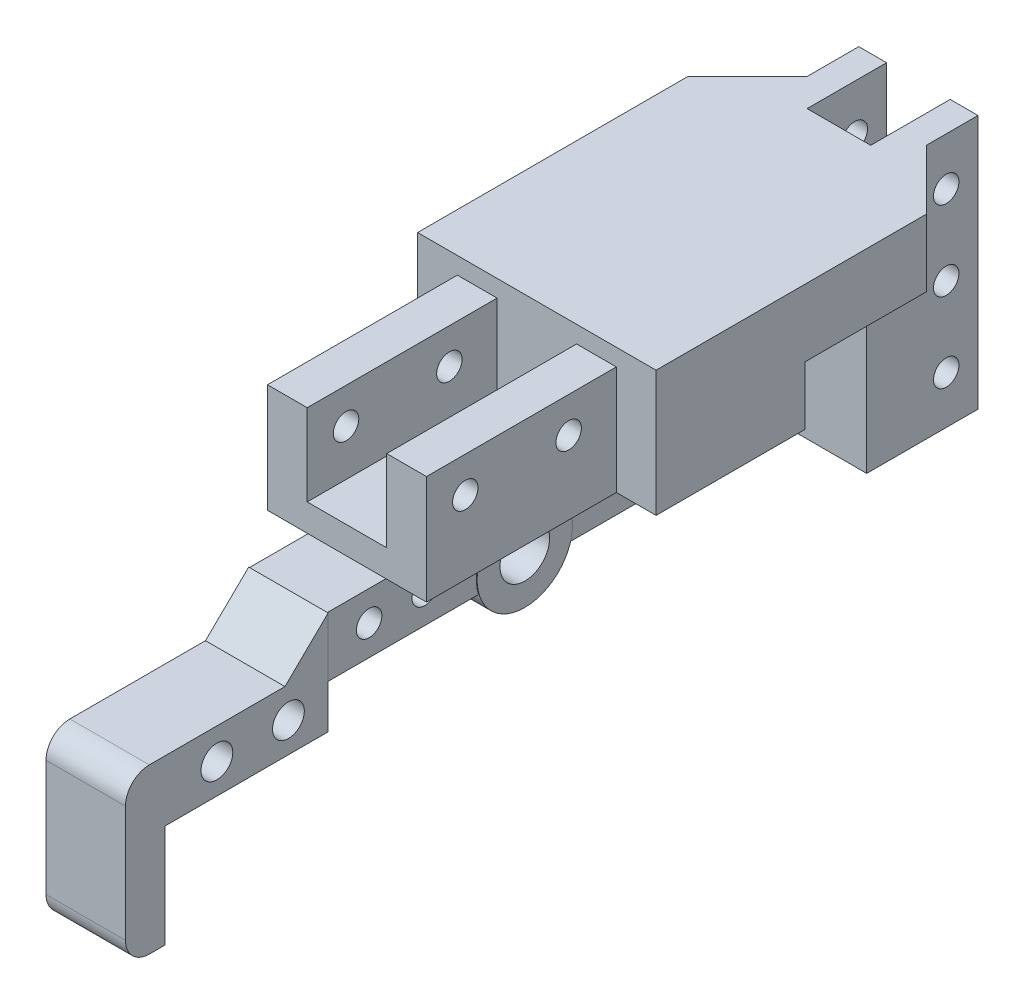
SolidWorks part; units mm, degrees
ref_plane "前视基准面" through (0, 0, 0) normal (0, 0, 1) x (1, 0, 0)
ref_plane "上视基准面" through (0, 0, 0) normal (0, 1, 0) x (1, 0, 0)
ref_plane "右视基准面" through (0, 0, 0) normal (1, 0, 0) x (0, 0, -1)
sketch "草图2" plane through (0, 0, 0) normal (1, 0, 0) x (0, 0, -1)
  line L0 (7, 0) -> (32.5, 0) construction
  line L2 (44.75, 3.775) -> (-5.25, 3.775)
  line L3 (44.75, 3.775) -> (44.75, -3.775)
  line L4 (44.75, -3.775) -> (-5.25, -3.775)
  line L5 (-5.25, 3.775) -> (-5.25, -3.775)
  line L6 (44.75, 3.775) -> (-5.25, -3.775) construction
  line L7 (44.75, -3.775) -> (-5.25, 3.775) construction
  circle A0 centre (0, 0) radius 1.6
  circle A1 centre (7, 0) radius 1.6
  circle A2 centre (32.5, 0) radius 1.6
  circle A3 centre (39.5, 0) radius 1.6
  point P9 (19.75, 0)
  dimension "D1" = 25.5
  dimension "D2" = 7
  dimension "D3" = 3.775
extrude "凸台-拉伸1" add sketch "草图2" along normal mid plane 9.8
sketch "草图3" plane through (0, 0, 0) normal (1, 0, 0) x (0, 0, -1)
  line L0 (7, 13) -> (20, 13) construction
  line L1 (2.1144, 3.775) -> (2.1144, 17.4551)
  line L2 (44.75, 3.775) -> (-5.25, 3.775) construction
  line L3 (2.1144, 17.4551) -> (26, 17.4551)
  line L4 (26, 17.4551) -> (26, 3.775)
  line L5 (26, 3.775) -> (2.1144, 3.775)
  circle A0 centre (7, 13) radius 1.6
  circle A1 centre (20, 13) radius 1.6
  point P0 (7, 0)
  point P6 (13.5, 13)
  dimension "D1" = 13
  dimension "D3" = 3.2
  dimension "D4" = 3.2
  dimension "D2" = 6
extrude "凸台-拉伸2" add sketch "草图3" along normal mid plane 20
sketch "草图4" plane through (0, 0, -2.1144) normal (0, 0, 1) x (1, 0, 0)
  line L0 (10, 17.4551) -> (-10, 17.4551) construction
  line L1 (5, 7.1905) -> (-5, 7.1905)
  line L2 (5, 7.1905) -> (5, 17.4551)
  line L3 (5, 17.4551) -> (-5, 17.4551)
  line L4 (-5, 7.1905) -> (-5, 17.4551)
  line L5 (5, 7.1905) -> (-5, 17.4551) construction
  line L6 (5, 17.4551) -> (-5, 7.1905) construction
  point P0 (0, 12.3228)
extrude "切除-拉伸1" cut sketch "草图4" against normal through all
sketch "草图6" plane through (0, 0, 0) normal (1, 0, 0) x (0, 0, -1)
  line L0 (70, 3.6) -> (70, 13.6) construction
  line L2 (74, -12.4) -> (60, -12.4)
  line L3 (74, -12.4) -> (74, 19.6)
  line L4 (74, 19.6) -> (60, 19.6)
  line L5 (60, -12.4) -> (60, 19.6)
  line L6 (74, -12.4) -> (60, 19.6) construction
  line L7 (74, 19.6) -> (60, -12.4) construction
  circle A0 centre (70, 3.6) radius 1.6
  circle A1 centre (70, 13.6) radius 1.6
  circle A2 centre (70, -6.4) radius 1.6
  point P4 (70, 8.6)
  point P9 (67, 3.6)
  dimension "D1" = 60
  dimension "D6" = 10
  dimension "D2" = 3.6
  dimension "D3" = 10
  dimension "D4" = 4
  dimension "D5" = 14
  dimension "D7" = 6
  dimension "D8" = 6
extrude "凸台-拉伸4" add sketch "草图6" along normal mid plane 15 separate body
sketch "草图7" plane through (0, 0, -74) normal (0, 0, 1) x (1, 0, 0)
  line L0 (7.5, 19.6) -> (-7.5, 19.6) construction
  line L1 (-4, 19.6) -> (4, 19.6)
  line L2 (-4, 19.6) -> (-4, -12.4)
  line L3 (-4, -12.4) -> (4, -12.4)
  line L4 (4, 19.6) -> (4, -12.4)
  line L5 (7.5, -12.4) -> (-7.5, -12.4) construction
extrude "切除-拉伸2" cut sketch "草图7" along normal blind 10
sketch "草图8" plane through (0, 0, 0) normal (1, 0, 0) x (0, 0, -1)
  line L0 (26, 3.775) -> (26, 17.4551) construction
  line L1 (60, 19.6) -> (26, 19.6)
  line L2 (60, 19.6) -> (60, 11.1399)
  line L3 (60, 11.1399) -> (44.75, 11.1399)
  line L4 (26, 19.6) -> (26, 11.1399)
  line L7 (26, 11.1399) -> (26, 3.775)
  line L8 (26, 3.775) -> (44.75, 3.775)
  line L9 (44.75, 11.1399) -> (44.75, 3.775)
extrude "凸台-拉伸5" add sketch "草图8" along normal mid plane 30
chamfer "倒角1" distance 7.5 angle 45 2 edges at (-7.5, 15.37, -60) (7.5, 15.37, -60)
sketch "草图10" plane through (0, 0, 0) normal (1, 0, 0) x (0, 0, -1)
  line L0 (-5.25, 3.775) -> (-5.25, -9.1767)
  line L1 (-5.25, -9.1767) -> (-25.75, -9.1767)
  line L2 (-25.75, -9.1767) -> (-25.75, -22.145)
  line L3 (-30.75, -22.145) -> (-30.75, -1.5241)
  line L5 (-30.75, -22.145) -> (-25.75, -22.145)
  line L6 (-30.75, -1.5241) -> (-10.6887, -1.5241)
  line L7 (-10.6887, -1.5241) -> (-5.25, 3.775)
  circle A0 centre (-10.25, -5.4017) radius 2
  circle A1 centre (-19.25, -5.4017) radius 2
  dimension "D3" = 4
  dimension "D4" = 4
  dimension "D1" = 20.5
  dimension "D2" = 5
  dimension "D5" = 9
  dimension "D6" = 5
extrude "凸台-拉伸6" add sketch "草图10" along normal mid plane 10
fillet "圆角1" radius 3 2 edges at (0, -22.145, 30.75) (0, -1.5241, 30.75)
sketch "草图11" plane through (0, 0, 0) normal (1, 0, 0) x (0, 0, -1)
  circle A1 centre (19.4875, -2) radius 3.125
  circle A2 centre (19.4875, -2) radius 6
  dimension "D1" = 6.25
  dimension "D2" = 12
  dimension "D3" = 2
extrude "凸台-拉伸7" add sketch "草图11" along normal mid plane 10
sketch "草图12" plane through (0, 0, 0) normal (1, 0, 0) x (0, 0, -1)
  circle A0 centre (19.4875, -2) radius 3.125 construction
  circle A1 centre (19.4875, -2) radius 3.125
extrude "切除-拉伸3" cut sketch "草图12" against normal through all both and the other way through all
